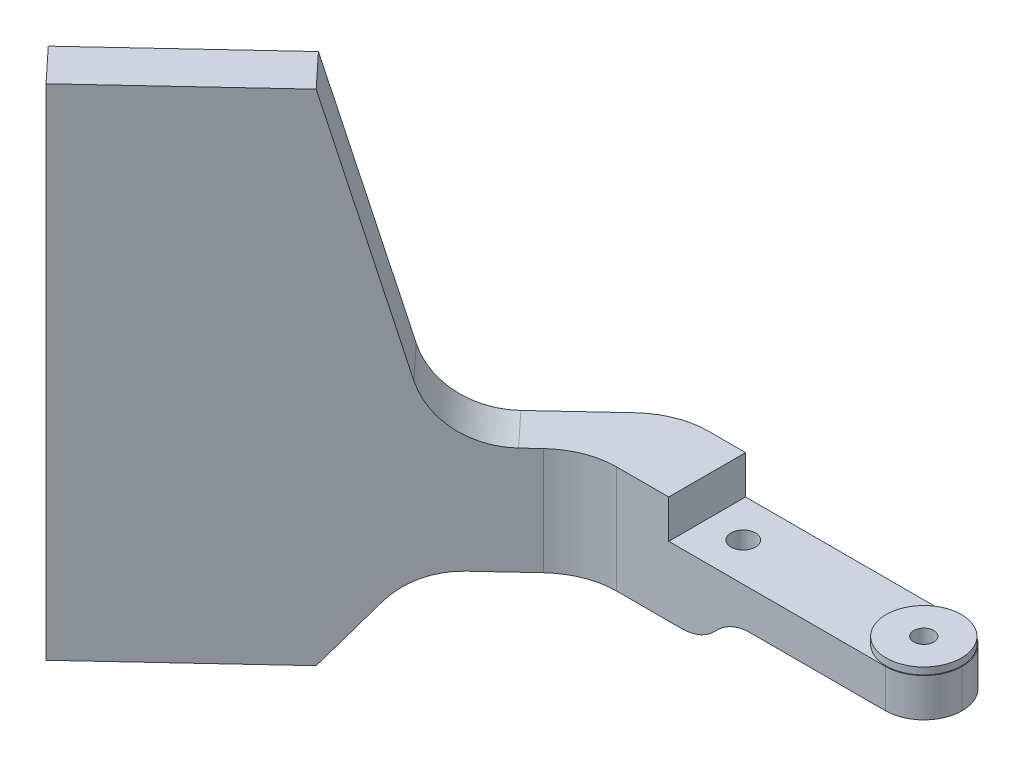
SolidWorks part; units mm, degrees
ref_plane "Front" through (0, 0, 0) normal (0, 0, 1) x (1, 0, 0)
ref_plane "Top" through (0, 0, 0) normal (0, 1, 0) x (1, 0, 0)
ref_plane "Right" through (0, 0, 0) normal (1, 0, 0) x (0, 0, -1)
sketch "Sketch1" plane through (0, 0, 0) normal (0, 1, 0) x (1, 0, 0)
  line L0 (0, 10) -> (0, 0)
  line L1 (0, 0) -> (42, 0)
  line L3 (0, 10) -> (42, 10)
  line L4 (42, 0) -> (42, 10)
  line L9 (0, 10) -> (-42.4185, -29.5559)
  line L10 (-42.4185, -29.5559) -> (-38.3265, -33.944)
  line L11 (0, 10) -> (4.092, 5.6119)
  line L12 (-38.3265, -33.944) -> (4.092, 5.6119)
  line L13 (0, 0) -> (-1.926, 0)
  line L14 (-1.926, 0) -> (0, 1.796)
  line L15 (0, 1.796) -> (0, 0)
  dimension "D1" = 10
  dimension "D2" = 42
  dimension "D3" = 223
  dimension "D4" = 58
  dimension "D5" = 6
  dimension "D6" = 270
extrude "Boss-Extrude1" add sketch "Sketch1" along normal blind 5 contours L10 L12 L1 L0 L9 | L1 L12 L11 L0 | L12 L1 L4 L3 L11 | L13 L0 L12 region at (1.364, 0, -5.8026) region at (-20.2035, 0, 12.8728) region at (21.8174, 0, -4.9666) region at (-0.642, 0, -0.5987)
fillet "Fillet1" radius 5 2 edges at (42, 2.5, 0) (42, 2.5, -10)
sketch "Sketch2" plane through (0, 5, 0) normal (0, 1, 0) x (1, 0, 0)
  circle A0 centre (37, 5) radius 1.3
extrude "Cut-Extrude1" cut sketch "Sketch2" against normal blind 10
sketch "Sketch3" plane through (0, 5, 0) normal (0, 1, 0) x (1, 0, 0)
  line L0 (-42.4185, -29.5559) -> (-38.3265, -33.944)
  line L1 (-38.3265, -33.944) -> (-20.1263, -16.972)
  line L2 (-38.3265, -33.944) -> (-1.926, 0) construction
  line L3 (-20.1263, -16.972) -> (-24.2183, -12.5839)
  line L4 (0, 10) -> (-42.4185, -29.5559) construction
  line L5 (-24.2183, -12.5839) -> (-42.4185, -29.5559)
extrude "Boss-Extrude2" add sketch "Sketch3" along normal blind 45
sketch "Sketch4" plane through (0, 0, 0) normal (0, -1, 0) x (1, 0, 0)
  line L0 (-42.4185, 29.5559) -> (-38.3265, 33.944)
  line L1 (-38.3265, 33.944) -> (-20.1263, 16.972)
  line L2 (-38.3265, 33.944) -> (-1.926, 0) construction
  line L3 (-20.1263, 16.972) -> (-24.2183, 12.5839)
  line L4 (0, -10) -> (-42.4185, 29.5559) construction
  line L5 (-24.2183, 12.5839) -> (-42.4185, 29.5559)
extrude "Boss-Extrude3" add sketch "Sketch4" along normal blind 15
sketch "Sketch5" plane through (-4.9878, 0, -5.3488) normal (-0.682, 0, -0.7314) x (-0.7314, 0, 0.682)
  line L0 (26.2943, -15) -> (26.2943, 0)
  line L1 (26.2943, 0) -> (13.889, 0)
  line L2 (-6.82, 0) -> (26.2943, 0) construction
  line L3 (13.889, 0) -> (26.2943, -15)
  line L4 (13.889, 5) -> (26.2943, 50)
  line L5 (-6.82, 5) -> (26.2943, 5) construction
  line L6 (26.2943, 50) -> (26.2943, 5)
  line L7 (26.2943, 5) -> (13.889, 5)
extrude "Boss-Extrude4" add sketch "Sketch5" against normal blind 6
sketch "Sketch6" plane through (0, 0, 0) normal (0, -1, 0) x (1, 0, 0)
  circle A0 centre (37, -5) radius 4.9
  circle A1 centre (37, -5) radius 1.3
extrude "Boss-Extrude5" add sketch "Sketch6" against normal blind 5.9
sketch "Sketch8" plane through (0, 0, 0) normal (0, -1, 0) x (1, 0, 0)
  line L0 (0, -10) -> (-19.6819, 8.3537)
  line L1 (-24.2183, 12.5839) -> (-15.1456, 4.1235) construction
  line L6 (-19.6819, 8.3537) -> (-15.5899, 12.7418)
  line L7 (-20.1263, 16.972) -> (-11.0536, 8.5116) construction
  line L8 (-15.5899, 12.7418) -> (8.7977, -10)
  line L9 (0, -10) -> (37, -10) construction
  line L10 (8.7977, -10) -> (0, -10)
extrude "Boss-Extrude6" add sketch "Sketch8" along normal blind 4
sketch "Sketch9" plane through (0, 5, 0) normal (0, 1, 0) x (1, 0, 0)
  line L3 (-17.565, -6.3796) -> (-24.2183, -12.5839) construction
  line L4 (-20.8916, -9.4817) -> (0, 10)
  line L6 (-20.8916, -9.4817) -> (-16.7996, -13.8699)
  line L7 (-20.1263, -16.972) -> (-11.0536, -8.5116) construction
  line L9 (-16.7996, -13.8699) -> (8.7977, 10)
  line L10 (0, 10) -> (37, 10) construction
  line L11 (8.7977, 10) -> (0, 10)
  line L12 (37, 0) -> (-1.926, 0) construction
  line L13 (8.7977, 0) -> (-1.926, 0)
  line L14 (-1.926, 0) -> (8.7977, 10)
  line L15 (8.7977, 10) -> (17.9505, 10)
  line L16 (17.9505, 10) -> (17.9505, 0)
  line L17 (17.9505, 0) -> (8.7977, 0)
  line M3 (-1.926, 0) -> (37, 0)
  line M6 (37, 10) -> (0, 10)
sketch "Sketch10" plane through (0, 5, 0) normal (0, 1, 0) x (1, 0, 0)
  line L0 (8.7977, 10) -> (8.7977, 0)
  line L1 (8.7977, 0) -> (-1.926, 0)
  line L2 (-1.926, 0) -> (-16.7996, -13.8699)
  line L3 (-16.7996, -13.8699) -> (-20.8916, -9.4817)
  line L4 (-20.8916, -9.4817) -> (0, 10)
  line L5 (0, 10) -> (8.7977, 10)
extrude "Boss-Extrude7" add sketch "Sketch10" along normal blind 5
extrude "Boss-Extrude8" add sketch "Sketch9" against normal blind 9 contours L16 L9 M6 M3 region at (10.3631, 5, -4.3843)
chamfer "Chamfer1" distance 5 angle 45 1 edges at (17.9505, -4, -5)
fillet "Fillet2" radius 6 2 edges at (16.9505, 0, -5) (12.9505, -4, -5)
sketch "Sketch11" plane through (0, 5, 0) normal (0, 1, 0) x (1, 0, 0)
  circle A0 centre (13.5, 5) radius 1.6
extrude "Cut-Extrude2" cut sketch "Sketch11" against normal blind 10
fillet "Fillet3" radius 10 4 edges at (0, 3, -10) (-15.519, -4, 8.5736) (-14.1077, 10, 7.2576) (-1.926, 3, 0)
